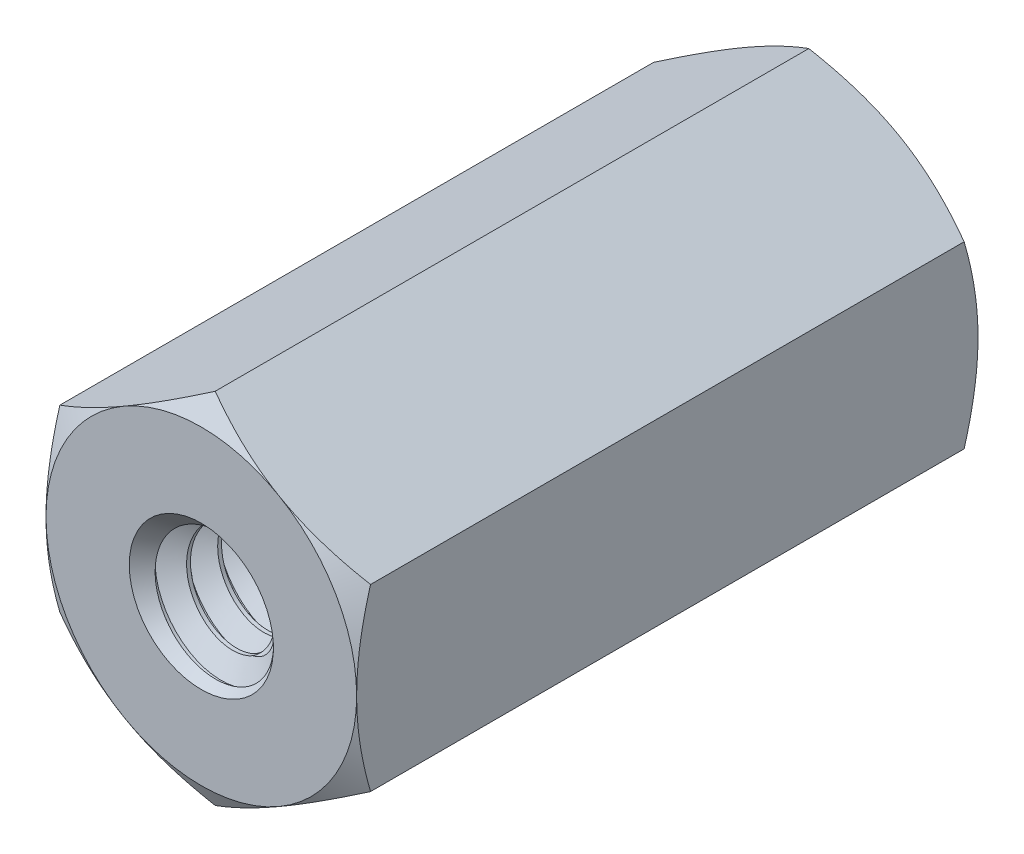
SolidWorks part; units mm, degrees
ref_plane "Front Plane" through (0, 0, 0) normal (0, 0, 1) x (1, 0, 0)
ref_plane "Top Plane" through (0, 0, 0) normal (0, 1, 0) x (1, 0, 0)
ref_plane "Right Plane" through (0, 0, 0) normal (1, 0, 0) x (0, 0, -1)
sketch "Sketch3" plane through (0, 0, 0) normal (1, 0, 0) x (0, 0, -1)
  line L0 (-6.35, 0) -> (6.35, 0) construction
  line L1 (0, 3.175) -> (0, -3.175) construction
  line L2 (-6.35, 1.4224) -> (-6.35, -1.4224) construction
  point P2 (-9.525, 0)
  point P3 (9.525, 0)
  dimension "Length" = 12.7
  dimension "Min Thread Length" = 15.875
  dimension "D1" = 15.875
  dimension "Thread Dia" = 2.8448
  dimension "Hex" = 6.35
sketch "Sketch1" plane through (0, 0, 0) normal (0, 0, 1) x (1, 0, 0)
  line L1 (0, 3.6662) -> (-3.175, 1.8331)
  line L2 (-3.175, 1.8331) -> (-3.175, -1.8331)
  line L3 (-3.175, -1.8331) -> (0, -3.6662)
  line L4 (0, -3.6662) -> (3.175, -1.8331)
  line L5 (3.175, -1.8331) -> (3.175, 1.8331)
  line L6 (3.175, 1.8331) -> (0, 3.6662)
  circle A0 centre (0, 0) radius 3.175 construction
  circle A1 centre (0, 0) radius 1.4224
extrude "Extrude1" add sketch "Sketch1" along normal up to vertex (6.35 mm away) and the other way up to vertex (6.35 mm away) up to point (0, 0, 6.35) other way up to point (0, 0, -6.35)
sketch "Sketch11" plane through (0, 0, -6.35) normal (0, 0, -1) x (-1, 0, 0)
  circle A0 centre (0, 0) radius 1.4224 construction
  circle A1 centre (0, 0) radius 1.4224
curve "Helix/Spiral1" pitch 0.635 height 13.335 radius 1.4224 centre (0, 0, -6.35) axis (0, 0, 1) start towards (0, 1, 0) parameters "Pitch"=0.635
sketch "Sketch12" plane through (0, 0, 0) normal (1, 0, 0) x (0, 0, -1)
  line L0 (6.9056, 1.4224) -> (6.35, 1.4224)
  line L1 (6.9056, 1.4224) -> (6.6675, 1.01)
  line L2 (6.6675, 1.01) -> (6.5881, 1.01)
  line L3 (6.5881, 1.01) -> (6.35, 1.4224)
  line L4 (6.6278, 1.01) -> (6.6278, 1.4224) construction
  line L5 (6.7866, 1.2162) -> (6.4691, 1.2162) construction
  dimension "D1" = 0.0794
  dimension "D2" = 0.3175
  dimension "D3" = 60
sweep "Sweep1" add profiles "Sketch12" path "Helix/Spiral1"
sketch "Sketch6" plane through (0, 0, -6.35) normal (0, 0, -1) x (-1, 0, 0)
  line L6 (0, 3.6662) -> (-3.175, 1.8331)
  line L7 (-3.175, 1.8331) -> (-3.175, -1.8331)
  line L8 (-3.175, -1.8331) -> (0, -3.6662)
  line L9 (0, -3.6662) -> (3.175, -1.8331)
  line L10 (3.175, -1.8331) -> (3.175, 1.8331)
  line L11 (3.175, 1.8331) -> (0, 3.6662)
  line L12 (0, 3.6662) -> (-3.175, 1.8331)
  line L13 (-3.175, 1.8331) -> (-3.175, -1.8331)
  line L14 (-3.175, -1.8331) -> (0, -3.6662)
  line L15 (0, -3.6662) -> (3.175, -1.8331)
  line L16 (3.175, -1.8331) -> (3.175, 1.8331)
  line L17 (3.175, 1.8331) -> (0, 3.6662)
  dimension "D1" = 0
extrude "Extrude2" cut sketch "Sketch6" along normal through all
sketch "Sketch7" plane through (0, 0, -6.35) normal (0, 0, -1) x (-1, 0, 0)
  circle A2 centre (0, 0) radius 1.4732
  circle A3 centre (0, 0) radius 1.4732
  dimension "D1" = 0.0508
extrude "Extrude3" cut sketch "Sketch7" against normal through all draft 43
sketch "Sketch8" plane through (0, 0, -6.35) normal (0, 0, -1) x (-1, 0, 0)
  circle A0 centre (0, 0) radius 3.175 construction
  circle A1 centre (0, 0) radius 3.175
extrude "Extrude4" cut sketch "Sketch8" against normal through all draft 60 flip side to cut
mirror "Mirror1" about plane through (0, 0, 0) normal (0, 0, 1) of "Extrude2", "Extrude3", "Extrude4"
sketch "Sketch9" [suppressed] plane through (0, 0, 0) normal (1, 0, 0) x (0, 0, -1)
  line L1 (-22.225, 3.2258) -> (22.225, 3.2258)
  line L2 (-22.225, 3.2258) -> (-22.225, 0)
  line L3 (-22.225, 0) -> (22.225, 0)
  line L4 (22.225, 3.2258) -> (22.225, 0)
  line L7 (-38.1, 0) -> (38.1, 0) construction
revolve "Revolve" [suppressed] add sketch "Sketch9" angle 360 about L0
sketch "Sketch10" [suppressed] plane through (0, 0, 0) normal (1, 0, 0) x (0, 0, -1)
  line L0 (38.1, 3.175) -> (22.225, 3.175)
  line L1 (-38.1, 3.175) -> (-22.225, 3.175)
  line L2 (22.225, 3.175) -> (22.225, -3.175)
  line L3 (-38.1, -3.2258) -> (-22.225, -3.2258)
  line L4 (-22.225, 3.175) -> (-22.225, -3.2258)
  line L5 (22.225, -3.175) -> (38.1, -3.175)
ref_axis "Axis1" through (0, 0, 10.4775) along (0, 0, -1)
equation "\"D1@Sketch3\" = \"Min Thread Length@Sketch3\""
equation "\"D3@Helix/Spiral1\" = \"Length@Sketch3\"+\"Pitch@Helix/Spiral1\""
equation "\"D1@Sketch12\" = \"Pitch@Helix/Spiral1\"*.125"
equation "\"D2@Sketch12\" = \"Pitch@Helix/Spiral1\"*.5"
